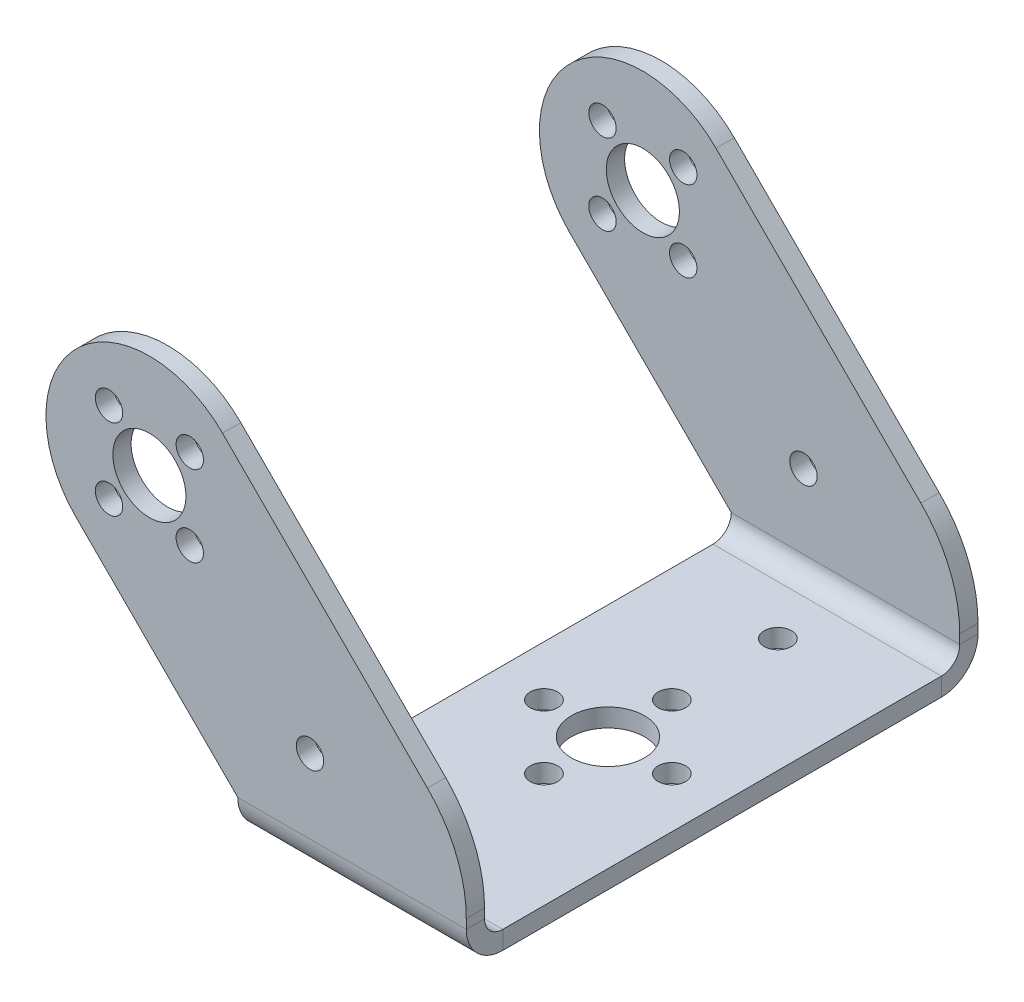
SolidWorks part; units mm, degrees
note: The reader was unsure of these and kept them because the rebuilt part matched: flange length of "Edge-Flange1".
material "6063-T4"
ref_plane "Plan de face" through (0, 0, 0) normal (0, 0, 1) x (1, 0, 0)
ref_plane "Plan de dessus" through (0, 0, 0) normal (0, 1, 0) x (1, 0, 0)
ref_plane "Plan de droite" through (0, 0, 0) normal (1, 0, 0) x (0, 0, -1)
ref_plane "Plan1" through (0, 0, 0) normal (0, 0, -1) x (-1, 0, 0)
sketch "Sketch8" plane through (0, 0, 0) normal (0, 0, 1) x (1, 0, 0)
  line L0 (-30.1777, 33.6848) -> (0, 0) construction
  line L1 (-12.5, 0) -> (12.5, 0)
  line L2 (-12.5, 0) -> (-30.1777, 17.6777)
  line L3 (8.253, 11.2612) -> (-14.1705, 33.6848)
  line L4 (12.5, 1.0082) -> (12.5, 0)
  line L5 (-22.1741, 37) -> (-22.1741, 0) construction
  arc A0 (-30.1777, 17.6777) -> (-14.1705, 33.6848) centre (-22.1741, 25.6812) cw
  arc A1 (8.253, 11.2612) -> (12.5, 1.0082) centre (-2, 1.0082) cw
  dimension "D5" = 14.5
  dimension "D1" = 25
  dimension "D3" = 45
  dimension "D2" = 25
  dimension "D4" = 37
base flange "Base-Flange1" sketch "Sketch8" thickness 2 reverse thickness direction no parameters "D1"=2
edge flange "Edge-Flange1" sketch "Sketch14" flange angle 90 flange length 26 flange position bend outside bend radius 2 thickness 2 relief rectangular parameters "D6"=10
sketch "Sketch14" plane through (0, 0, -2) normal (0, -1, 0) x (-1, 0, 0)
  line L0 (12.5, 0) -> (-12.5, 0) construction
  line L1 (12.5, 0) -> (-12.5, 0)
  line L2 (-12.5, 0) -> (-12.5, 26)
  line L3 (-12.5, 26) -> (12.5, 26)
  line L4 (12.5, 26) -> (12.5, 0)
bend "EdgeBend1" bend radius 2 bend angle 90 parameters "D5"=1
sketch "Sketch19" plane through (0, 0, 0) normal (0, 0, 1) x (1, 0, 0)
  circle A0 centre (-22.1741, 25.6812) radius 4
  dimension "D1" = 8
extrude "Cut-Extrude2" cut sketch "Sketch19" against normal through all normal cut yes
hole_wizard "M3x0.5 Tapped Hole1" positions "Sketch21" profile "Sketch20" tap size "M3x0.5" standard "ANSI Metric" end condition through all
sketch "Sketch21" plane through (0, 0, 0) normal (0, 0, 1) x (1, 0, 0)
  line L0 (-26.5935, 30.1007) -> (-17.7547, 21.2618) construction
  line L2 (-17.7547, 30.1007) -> (-26.5935, 21.2618) construction
  line L4 (-4.6025, 8.1096) -> (-17.7547, 21.2618) construction
  line L6 (-30.1777, 17.6777) -> (-12.5, 0) construction
  circle A0 centre (-22.1741, 25.6812) radius 6.25 construction
  point P0 (-26.5935, 30.1007)
  point P2 (-26.5935, 21.2618)
  point P4 (-17.7547, 21.2618)
  point P6 (-17.7547, 30.1007)
  point P22 (-22.1741, 25.6812)
  point P30 (-4.6025, 8.1096)
  dimension "D1" = 12.5
  dimension "D2" = 18.6
sketch "Sketch20" plane through (-26.5935, 30.1007, 0) normal (1, 0, 0) x (0, -1, 0)
  line L0 (0, 0) -> (0, 28)
  line L1 (0, 28) -> (1.5, 28)
  line L2 (1.5, 28) -> (1.5, 0)
  line L5 (1.5, 0) -> (0, 0)
  line L11 (0, -6.35) -> (0, 107.95) construction
  dimension "Thread Major Dia." = 3
  dimension "Thru Tap Drill Depth" = 28
mirror "Mirror1" about plane through (12.5, -4, -28) normal (0, 0, 1) of bodies 153
bend "MirrorBend1" bend radius 2 bend angle 90 parameters "D5"=2
sketch "Sketch22" plane through (0, -2, 0) normal (0, 1, 0) x (1, 0, 0)
  line L0 (-12.5, 28) -> (12.5, 28) construction
  line L1 (-12.5, 4) -> (-12.5, 52) construction
  line L2 (12.5, 52) -> (12.5, 4) construction
  circle A0 centre (0, 28) radius 4
  dimension "D1" = 8
extrude "Cut-Extrude3" cut sketch "Sketch22" against normal through all normal cut yes
hole_wizard "M3x0.5 Tapped Hole2" positions "Sketch24" profile "Sketch23" tap size "M3x0.5" standard "ANSI Metric" end condition through all
sketch "Sketch24" plane through (0, -2, 0) normal (0, 1, 0) x (1, 0, 0)
  line L2 (7, 28) -> (-7, 28) construction
  line L4 (0, 21) -> (0, 35) construction
  line L5 (0, 46.6) -> (0, 9.4) construction
  circle A0 centre (0, 28) radius 7 construction
  point P0 (7, 28)
  point P2 (-7, 28)
  point P4 (0, 35)
  point P6 (0, 21)
  point P8 (0, 9.4)
  point P10 (0, 46.6)
  point P28 (0, 28)
  point P33 (0, 28)
  dimension "D2" = 14
  dimension "D1" = 18.6
sketch "Sketch23" plane through (7, -2, -28) normal (1, 0, 0) x (0, 0, 1)
  line L0 (0, 0) -> (0, 2)
  line L1 (0, 2) -> (1.5, 2)
  line L2 (1.5, 2) -> (1.5, 0)
  line L5 (1.5, 0) -> (0, 0)
  line L11 (0, -6.35) -> (0, 107.95) construction
  dimension "Thread Major Dia." = 3
  dimension "Thru Tap Drill Depth" = 2
sketch "Bend-Lines1" [suppressed] plane through (0, 0, 0) normal (0, 1, 0) x (1, 0, 0)
sketch "Bounding-Box1" [suppressed] plane through (0, 0, 0) normal (0, 1, 0) x (1, 0, 0)
sheet metal parameters "Sheet-Metal48" thickness 2 parameters "D1"=1
flat pattern "Flat-Pattern56" [suppressed]
sketch "Bend-Lines3" plane through (0, 0, 0) normal (0, 1, 0) x (1, 0, 0)
sketch3d "Bounding-Box3" [suppressed]
  line L0 (-12.5, -50, 0) -> (-12.5, 12.5, 0) construction
  line L1 (12.5, -50, 0) -> (12.5, 12.5, 0) construction
  line L2 (-12.5, -50, 0) -> (12.5, -50, 0) construction
  line L3 (-12.5, 12.5, 0) -> (12.5, 12.5, 0) construction
sheet metal parameters "Sheet-Metal49" thickness 2 parameters "D1"=1
flat pattern "Flat-Pattern56"
sketch "Bend-Lines3" plane through (0, 0, 0) normal (0, 0, 1) x (1, 0, 0)
  line L0 (-12.5, 0.8219) -> (12.5, 0.8219) construction
  line L1 (-12.5, 0.8219) -> (12.5, 0.8219) construction
sketch3d "Bounding-Box3" [suppressed]
  line L0 (12.5, -100.3562, 0) -> (12.5, 12.5, 0) construction
  line L1 (-12.5, -100.3562, 0) -> (-12.5, 12.5, 0) construction
  line L2 (12.5, -100.3562, 0) -> (-12.5, -100.3562, 0) construction
  line L3 (12.5, 12.5, 0) -> (-12.5, 12.5, 0) construction
bend of the flat pattern "Flatten-<EdgeBend1>1"
sheet metal parameters "Sheet-Metal52" thickness 2 parameters "D1"=1
flat pattern "Flat-Pattern56"
sketch "Bend-Lines3" plane through (0, 0, 0) normal (0, 0, 1) x (1, 0, 0)
  line L0 (-12.5, -1.1781) -> (12.5, -1.1781) construction
  line L1 (-12.5, -1.1781) -> (12.5, -1.1781) construction
  line L2 (-12.5, -52.5343) -> (12.5, -52.5343) construction
  line L3 (-12.5, -52.5343) -> (12.5, -52.5343) construction
sketch3d "Bounding-Box3" [suppressed]
  line L0 (12.5, 12.5, 0) -> (12.5, -164.2123, 0) construction
  line L1 (-12.5, 12.5, 0) -> (-12.5, -164.2123, 0) construction
  line L2 (12.5, 12.5, 0) -> (-12.5, 12.5, 0) construction
  line L3 (12.5, -164.2123, 0) -> (-12.5, -164.2123, 0) construction
bend of the flat pattern "Flatten-<EdgeBend1>1"
sheet metal parameters "Sheet-Metal53" thickness 2 parameters "D1"=1
flat pattern "Flat-Pattern56"
sketch "Bend-Lines3" plane through (0, 0, 0) normal (0, 0, 1) x (1, 0, 0)
  line L0 (-12.5, -1.1781) -> (12.5, -1.1781) construction
  line L1 (-12.5, -1.1781) -> (12.5, -1.1781) construction
  line L2 (-12.5, -52.5343) -> (12.5, -52.5343) construction
  line L3 (-12.5, -52.5343) -> (12.5, -52.5343) construction
sketch3d "Bounding-Box3" [suppressed]
  line L0 (12.5, 12.5, 0) -> (12.5, -164.2123, 0) construction
  line L1 (-12.5, 12.5, 0) -> (-12.5, -164.2123, 0) construction
  line L2 (12.5, 12.5, 0) -> (-12.5, 12.5, 0) construction
  line L3 (12.5, -164.2123, 0) -> (-12.5, -164.2123, 0) construction
bend of the flat pattern "Flatten-<EdgeBend1>1"
sheet metal parameters "Sheet-Metal54" thickness 2 parameters "D1"=1
flat pattern "Flat-Pattern56" [suppressed]
sketch "Bend-Lines3" plane through (0, 0, 0) normal (0, 0, 1) x (1, 0, 0)
  line L0 (-12.5, -1.1781) -> (12.5, -1.1781) construction
  line L1 (-12.5, -1.1781) -> (12.5, -1.1781) construction
  line L2 (-12.5, -52.5343) -> (12.5, -52.5343) construction
  line L3 (-12.5, -52.5343) -> (12.5, -52.5343) construction
sketch3d "Bounding-Box3" [suppressed]
  line L0 (12.5, 12.5, 0) -> (12.5, -164.2123, 0) construction
  line L1 (-12.5, 12.5, 0) -> (-12.5, -164.2123, 0) construction
  line L2 (12.5, 12.5, 0) -> (-12.5, 12.5, 0) construction
  line L3 (12.5, -164.2123, 0) -> (-12.5, -164.2123, 0) construction
bend of the flat pattern "Flatten-<EdgeBend1>1"
bend of the flat pattern "Flatten-<MirrorBend1>3"
sheet metal parameters "Sheet-Metal55" thickness 2 parameters "D1"=1
flat pattern "Flat-Pattern56"
sketch "Bend-Lines3" plane through (0, 0, 0) normal (0, 0, 1) x (1, 0, 0)
  line L0 (-12.5, -2.3562) -> (12.5, -2.3562) construction
  line L1 (-12.5, -2.3562) -> (12.5, -2.3562) construction
  line L2 (-12.5, -55.0686) -> (12.5, -55.0686) construction
  line L3 (-12.5, -55.0686) -> (12.5, -55.0686) construction
sketch3d "Bounding-Box3" [suppressed]
  line L0 (34.6741, 11.3188, 0) -> (34.6741, -120.106, 0) construction
  line L1 (-11.3187, 11.3188, 0) -> (-11.3187, -120.106, 0) construction
  line L2 (34.6741, 11.3188, 0) -> (-11.3187, 11.3188, 0) construction
  line L3 (34.6741, -120.106, 0) -> (-11.3187, -120.106, 0) construction
bend of the flat pattern "Flatten-<EdgeBend1>1"
bend of the flat pattern "Flatten-<MirrorBend1>2"
sheet metal parameters "Sheet-Metal56" thickness 2 parameters "D1"=1
flat pattern "Flat-Pattern56"
sketch "Bend-Lines4" plane through (0, 0, 0) normal (0, 0, 1) x (1, 0, 0)
  line L0 (-12.5, -105.5343) -> (12.5, -105.5343) construction
  line L1 (-12.5, -1.1781) -> (12.5, -1.1781) construction
  line L2 (-12.5, -105.5343) -> (12.5, -105.5343) construction
  line L3 (-12.5, -1.1781) -> (12.5, -1.1781) construction
sketch3d "Bounding-Box4" [suppressed]
  line L0 (33.8457, 12.4903, 0) -> (33.8457, -172.2221, 0) construction
  line L1 (-12.4903, 12.4903, 0) -> (-12.4903, -172.2221, 0) construction
  line L2 (33.8457, 12.4903, 0) -> (-12.4903, 12.4903, 0) construction
  line L3 (33.8457, -172.2221, 0) -> (-12.4903, -172.2221, 0) construction
bend of the flat pattern "Flatten-<EdgeBend1>2"
bend of the flat pattern "Flatten-<MirrorBend1>1"
equation "\"D7@Edge-Flange1\"=52/2"
equation "\"D4@Sketch8\"=39-2"
